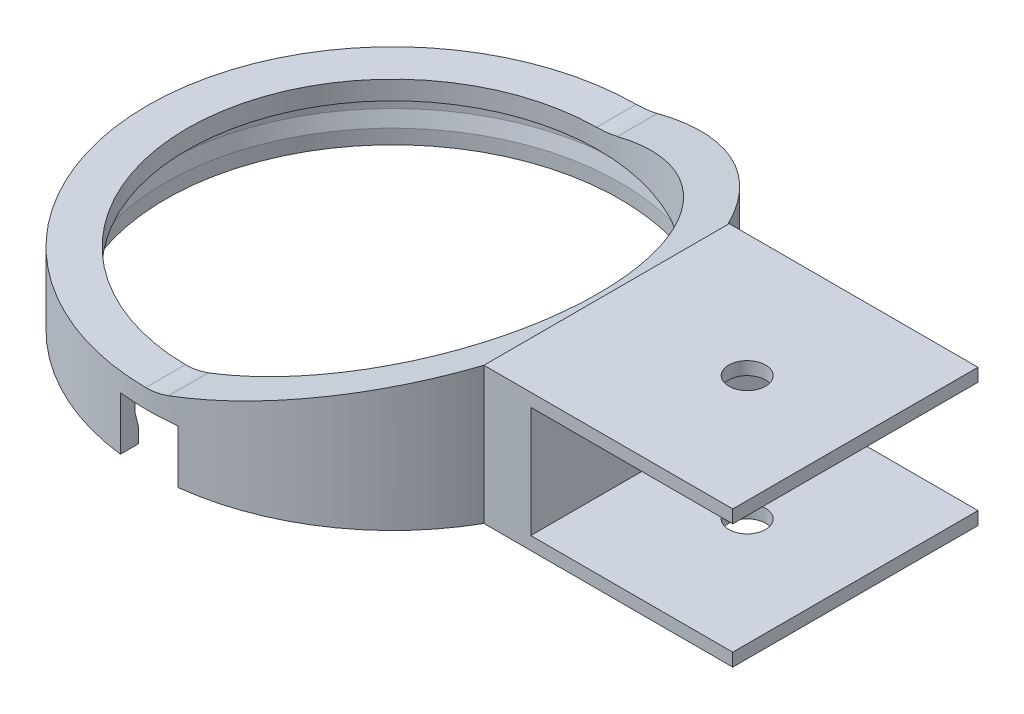
SolidWorks part; units mm, degrees
note: '?' marks a value the reader was unsure of.
ref_plane "Front Plane" through (0, 0, 0) normal (0, 0, 1) x (1, 0, 0)
ref_plane "Top Plane" through (0, 0, 0) normal (0, 1, 0) x (1, 0, 0)
ref_plane "Right Plane" through (0, 0, 0) normal (1, 0, 0) x (0, 0, -1)
sketch "Sketch1" plane through (0, 0, 0) normal (0, 1, 0) x (1, 0, 0)
  circle A0 centre (0, 0) radius 38.1
  circle A1 centre (0, 0) radius 36.195
  circle A2 centre (0, 0) radius 43.18
  dimension "D1" = 76.2
  dimension "D2" = 72.39
  dimension "D3" = 86.36
extrude "Boss-Extrude1" add sketch "Sketch1" along normal blind 2.54 contours A2 A0 | A0 A1
sketch "Sketch2" plane through (0, 0, 0) normal (0, -1, 0) x (1, 0, 0)
  circle A0 centre (0, 0) radius 40.64
  circle A2 centre (0, 0) radius 43.18
  dimension "D1" = 81.28
extrude "Boss-Extrude2" add sketch "Sketch2" along normal blind 4.318
sketch "Sketch3" plane through (0, 0, 0) normal (0, 0, 1) x (1, 0, 0)
  line L0 (0, 0) -> (-40.64, 0)
  line L1 (-40.64, 0) -> (-40.64, -4.318)
  line L2 (-40.005, -4.318) -> (-40.005, -6.858)
  line L3 (-40.64, -4.318) -> (-40.005, -6.858)
  line L4 (-40.64, -4.318) -> (-40.005, -4.318)
  line L5 (-40.005, -6.858) -> (-40.005, -9.398)
  line L6 (-40.005, -9.398) -> (-43.18, -9.398)
  line L7 (-40.64, -4.318) -> (-43.18, -4.318)
  line L8 (-43.18, -4.318) -> (-43.18, -9.398)
  line L9 (0, 0) -> (0, 20.6505)
  dimension "D1" = 40.64
  dimension "D2" = 4.318
  dimension "D3" = 0.635
  dimension "D4" = 2.54
  dimension "D5" = 2.54
  dimension "D6" = 3.175
  dimension "D7" = 2.54
revolve "Revolve1" add sketch "Sketch3" angle 360 about L9
ref_plane "Plane1" through (0, 0, 43.18) normal (0, 0, 1) x (1, 0, 0)
sketch "Sketch7" plane through (0, 0, 43.18) normal (0, 0, 1) x (1, 0, 0)
  line L0 (0, -10.16) -> (0, 0)
  line L1 (0, 0) -> (5.08, 0)
  line L2 (5.08, 0) -> (5.08, -10.16)
  line L3 (43.18, 2.54) -> (-43.18, 2.54) construction
  line L4 (0, 0) -> (-5.08, 0)
  line L5 (-5.08, 0) -> (-5.08, -10.16)
  line L6 (5.08, -10.16) -> (-5.08, -10.16)
  dimension "D1" = 5.08
  dimension "D2" = 10.16
  dimension "D3" = 10.16
  dimension "D4" = 2.54
  dimension "D5" = 5.08
extrude "Cut-Extrude1" cut sketch "Sketch7" against normal blind 12.7 contours L6 L0 L4 L5 | L6 L2 L1 L0
ref_plane "Plane2" through (43.18, 0, 0) normal (1, 0, 0) x (0, 0, -1)
sketch "Sketch8" plane through (43.18, 0, 0) normal (1, 0, 0) x (0, 0, -1)
  line L0 (0.1499, -9.398) -> (21.7399, -9.398)
  line L1 (-42.8801, -9.398) -> (43.18, -9.398) construction
  line L2 (21.7399, -9.398) -> (21.7399, 14.732)
  line L3 (21.7399, 14.732) -> (-21.4401, 14.732)
  line L4 (-21.4401, 14.732) -> (-21.4401, -9.398)
  line L5 (-21.4401, -9.398) -> (0.1499, -9.398)
  dimension "D1" = 24.13
  dimension "D2" = 21.59
  dimension "D3" = 21.59
sketch "Sketch12" plane through (0, 2.54, 0) normal (0, 1, 0) x (1, 0, 0)
  circle A0 centre (0, 0) radius 36.195
  circle A1 centre (0, 0) radius 43.18
extrude "Boss-Extrude3" add sketch "Sketch12" along normal blind 12.192
extrude "Boss-Extrude4" add sketch "Sketch8" against normal up to body contours L4 L5 L0 L2 L3
sketch "Sketch13" plane through (43.18, 0, 0) normal (1, 0, 0) x (0, 0, -1)
  line L0 (-21.4401, 14.732) -> (21.7399, 14.732)
  line L1 (21.7399, 14.732) -> (21.7399, -9.398)
  line L2 (21.7399, -9.398) -> (-21.4401, -9.398)
  line L3 (-21.4401, -9.398) -> (-21.4401, 14.732)
extrude "Boss-Extrude5" add sketch "Sketch13" along normal blind 38.1
sketch "Sketch14" plane through (81.28, 0, 0) normal (1, 0, 0) x (0, 0, -1)
  line L14 (-19.1541, 12.446) -> (-19.1541, -7.112)
  line L15 (-19.1541, -7.112) -> (19.4539, -7.112)
  line L16 (19.4539, -7.112) -> (19.4539, 12.446)
  line L17 (19.4539, 12.446) -> (-19.1541, 12.446)
  line L18 (-19.1541, 12.446) -> (-19.1541, -7.112)
  line L19 (-19.1541, -7.112) -> (19.4539, -7.112)
  line L20 (19.4539, -7.112) -> (19.4539, 12.446)
  line L21 (19.4539, 12.446) -> (-19.1541, 12.446)
  dimension "D1" = 2.286
extrude "Cut-Extrude2" cut sketch "Sketch14" against normal blind 35.56
sketch "Sketch17" plane through (0, 14.732, 0) normal (0, 1, 0) x (1, 0, 0)
  line L0 (81.28, 21.7399) -> (81.28, 0.1499)
  line L1 (81.28, 21.7399) -> (81.28, -21.4401) construction
  line L2 (81.28, 0.1499) -> (62.23, 0.1499)
  circle A0 centre (62.23, 0.1499) radius 3.2385
  dimension "D2" = 6.477
  dimension "D1" = 19.05
extrude "Cut-Extrude3" cut sketch "Sketch17" against normal blind 35.56
ref_plane "Plane3" through (30.5329, 0, 30.5329) normal (0.7071, 0, 0.7071) x (0, -1, 0)
ref_plane "Plane4" through (32.3289, 0, 32.3289) normal (0.7071, 0, 0.7071) x (0, -1, 0)
sketch "Sketch19" plane through (32.3289, 0, 32.3289) normal (0.7071, 0, 0.7071) x (0, -1, 0)
  line L0 (-14.732, 11.3428) -> (-3.6327, -25.0915)
  line L1 (-3.302, -27.3121) -> (-3.302, -33.5736)
  line L2 (-3.302, -33.5736) -> (-14.732, -33.5736)
  line L3 (-14.732, 43.18) -> (-14.732, -43.18) construction
  line L4 (-14.732, -33.5736) -> (-14.732, 11.3428)
  arc A0 (-3.6327, -25.0915) -> (-3.302, -27.3121) centre (-10.922, -27.3121) cw
  dimension "D1" = 7.62
  dimension "D2" = 11.43
ref_plane "Plane5" through (37.4811, 0, 21.4401) normal (0.868, 0, 0.4965) x (0.4965, 0, -0.868)
ref_plane "Plane6" through (39.6859, 0, 22.7012) normal (0.868, 0, 0.4965) x (0.4965, 0, -0.868)
sketch "Sketch20" plane through (39.6859, 0, 22.7012) normal (0.868, 0, 0.4965) x (0.4965, 0, -0.868)
  line L0 (0, 14.732) -> (-33.8088, 3.6792)
  line L1 (-36.1766, 3.302) -> (-48.7535, 3.302)
  line L2 (-48.7535, 3.302) -> (-48.7535, 14.732)
  line L3 (-48.7535, 14.732) -> (0, 14.732)
  arc A0 (-33.8088, 3.6792) -> (-36.1766, 3.302) centre (-36.1766, 10.922) cw
  dimension "D2" = 7.62
  dimension "D1" = 11.43
ref_axis "Axis1" through (0, 14.732, 0) along (0, -1, 0)?
curve "Curve7"
sketch "Sketch22" plane through (0, 0, 43.18) normal (0, 0, 1) x (1, 0, 0)
  line L0 (37.4811, 14.732) -> (1.6518, 3.302)
  line L1 (2.5006, 3.302) -> (-38.426, 3.302) construction
  line L2 (1.6518, 3.302) -> (-49.1626, 3.302)
  line L3 (-49.1626, 3.302) -> (-49.1626, 14.732)
  line L4 (-49.1626, 14.732) -> (37.4811, 14.732)
  dimension "D1" = 11.43
extrude "Cut-Extrude5" cut sketch "Sketch22" against normal blind 88.9
fillet "Fillet1" radius 12.7 2 edges at (1.6518, 3.302, -39.6528) (1.6518, 3.302, 39.6528)
sketch "Sketch23" plane through (0, 0, 21.4401) normal (0, 0, 1) x (1, 0, 0)
  line L0 (81.28, 14.732) -> (81.28, 12.446)
  line L1 (81.28, 14.732) -> (81.28, -9.398) construction
  line L2 (81.28, 12.446) -> (45.72, 12.446)
  line L3 (45.72, 12.446) -> (45.72, -7.112)
  line L4 (45.72, -7.112) -> (81.28, -7.112)
  line L5 (81.28, -7.112) -> (81.28, 12.446)
  dimension "D1" = 2.286
  dimension "D2" = 35.56
  dimension "D3" = 19.558
extrude "Cut-Extrude6" cut sketch "Sketch23" against normal blind 50.8 contours L2 L3 L4 L5
